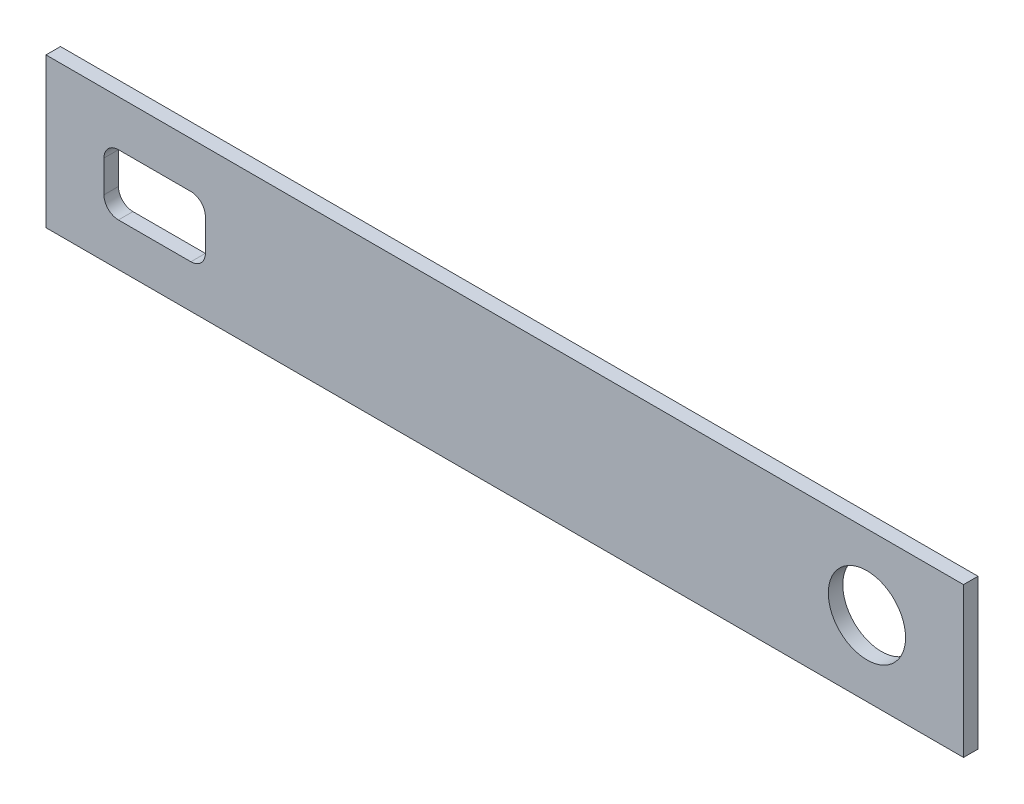
SolidWorks part; units mm, degrees
ref_plane "Front Plane" through (0, 0, 0) normal (0, 0, 1) x (1, 0, 0)
ref_plane "Top Plane" through (0, 0, 0) normal (0, 1, 0) x (1, 0, 0)
ref_plane "Right Plane" through (0, 0, 0) normal (1, 0, 0) x (0, 0, -1)
sketch "Sketch1" plane through (0, 0, 0) normal (0, 0, 1) x (1, 0, 0)
  line L1 (0, 0) -> (190, 0)
  line L2 (0, 0) -> (0, 31)
  line L3 (0, 31) -> (190, 31)
  line L4 (190, 0) -> (190, 31)
  line L5 (15, 21.5) -> (30, 21.5)
  line L6 (12, 18.5) -> (12, 11.9)
  line L7 (15, 8.9) -> (30, 8.9)
  line L8 (33, 18.5) -> (33, 11.9)
  circle A0 centre (170, 15.5) radius 8
  arc A1 (30, 8.9) -> (33, 11.9) centre (30, 11.9) ccw
  arc A2 (12, 11.9) -> (15, 8.9) centre (15, 11.9) ccw
  arc A3 (15, 21.5) -> (12, 18.5) centre (15, 18.5) ccw
  arc A4 (30, 21.5) -> (33, 18.5) centre (30, 18.5) cw
  point P13 (33, 8.9)
  point P16 (12, 8.9)
  point P21 (33, 21.5)
  dimension "D3" = 12.6
  dimension "D8" = 3
  dimension "D9" = 16
  dimension "D1" = 31
  dimension "D2" = 190
  dimension "D4" = 21
  dimension "D5" = 9.5
  dimension "D6" = 12
  dimension "D7" = 20
  dimension "D10" = 15.5
sheet metal parameters "Sheet-Metal1" thickness 3 parameters "D1"=0.7366
base flange "Base-Flange1" sketch "Sketch1" thickness 3 reverse thickness direction no parameters "D1"=0.7366
flat pattern "Flat-Pattern1" [suppressed]
sketch "Bend-Lines1" plane through (0, 0, 0) normal (0, 1, 0) x (1, 0, 0)
sketch3d "Bounding-Box1" [suppressed]
  line L0 (0, 0, 0) -> (-190, 0, 0) construction
  line L1 (0, 28, 0) -> (-190, 28, 0) construction
  line L2 (0, 0, 0) -> (0, 28, 0) construction
  line L3 (-190, 0, 0) -> (-190, 28, 0) construction
